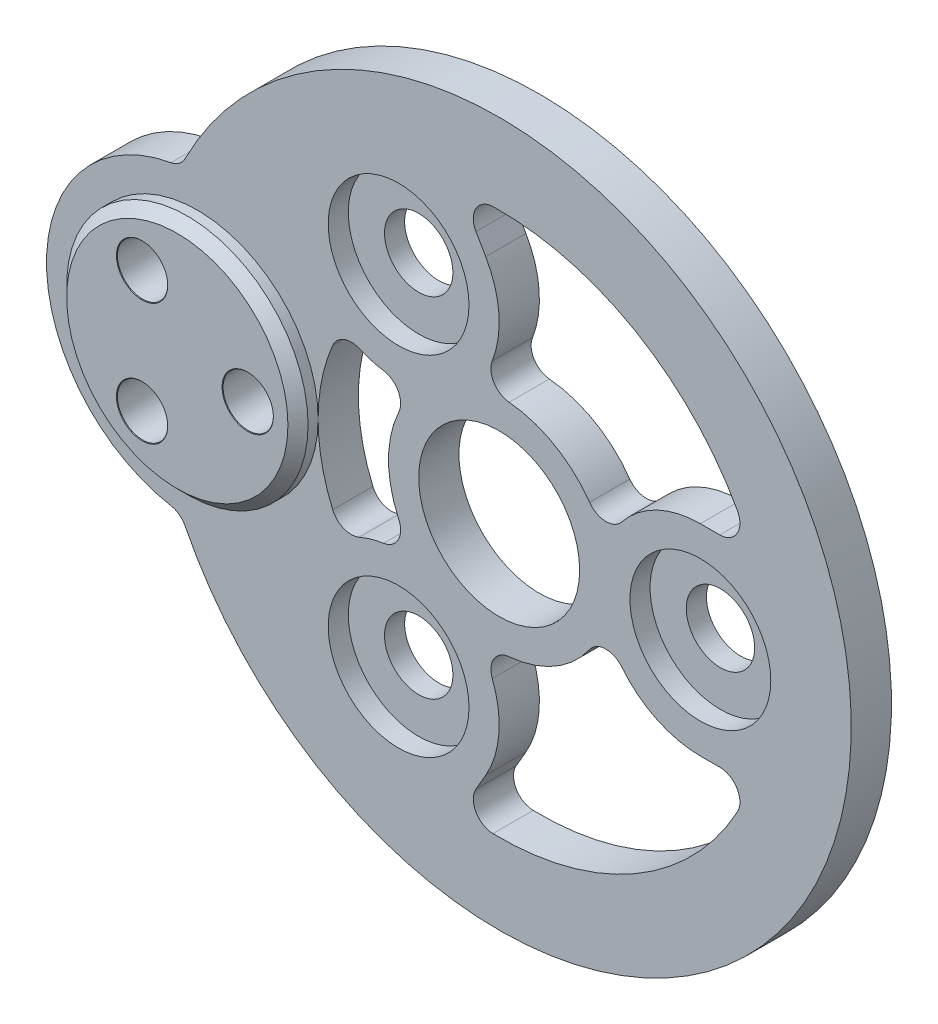
SolidWorks part; units mm, degrees
material "A2017"
ref_plane "正面" through (0, 0, 0) normal (0, 0, 1) x (1, 0, 0)
ref_plane "平面" through (0, 0, 0) normal (0, 1, 0) x (1, 0, 0)
ref_plane "右側面" through (0, 0, 0) normal (1, 0, 0) x (0, 0, -1)
sketch "ｽｹｯﾁ1" plane through (0, 0, 0) normal (0, 0, 1) x (1, 0, 0)
  line L0 (-15, 0) -> (0, 0) construction
  circle A0 centre (0, 0) radius 4
  arc A1 (-4.5, -6) -> (-4.5, 6) centre (0, 0) ccw
  arc A2 (-10.5, 6) -> (-10.5, -6) centre (-15, 0) ccw
  arc A3 (-10.5, 6) -> (-4.5, 6) centre (-7.5, 10) ccw
  arc A4 (-10.5, -6) -> (-4.5, -6) centre (-7.5, -10) cw
  dimension "D1" = 8
  dimension "D2" = 15
  dimension "D3" = 15
  dimension "D4" = 5
extrude "ﾎﾞｽ - 押し出し1" add sketch "ｽｹｯﾁ1" along normal blind 2
sketch "ｽｹｯﾁ6" plane through (0, 0, 2) normal (0, 0, 1) x (1, 0, 0)
  circle A0 centre (-15, 0) radius 6
  dimension "D1" = 12
extrude "ﾎﾞｽ - 押し出し3" add sketch "ｽｹｯﾁ6" along normal blind 1
sketch "ｽｹｯﾁ2" plane through (0, 0, 3) normal (0, 0, 1) x (1, 0, 0)
  circle A0 centre (-15, 0) radius 5 construction
  circle A1 centre (-11.5, 0) radius 1.5 construction
  circle A2 centre (-11.5, 0) radius 0.5
  dimension "D1" = 10
  dimension "D2" = 3
  dimension "D3" = 1
extrude "ｶｯﾄ - 押し出し1" cut sketch "ｽｹｯﾁ2" against normal blind 2
hole_wizard "M3x0.5 ねじ穴1" positions "ｽｹｯﾁ3" profile "ｽｹｯﾁ4" tap size "M3x0.5" standard "JIS" end condition through all
sketch "ｽｹｯﾁ3" plane through (0, 0, 3) normal (0, 0, 1) x (1, 0, 0)
  point P0 (-11.5, 0)
sketch "ｽｹｯﾁ4" plane through (-11.5, 0, 3) normal (1, 0, 0) x (0, -1, 0)
  line L0 (0, 0) -> (0, 3)
  line L1 (0, 3) -> (1.525, 3)
  line L2 (1.25, 2.725) -> (1.25, 0.025)
  line L3 (1.25, 0.025) -> (1.275, 0)
  line L5 (1.275, 0) -> (0, 0)
  line L6 (-1.25, 0.025) -> (-1.275, 0) construction
  line L7 (1.525, 3) -> (1.25, 2.725)
  line L8 (-1.525, 3) -> (-1.25, 2.725) construction
  line L11 (0, -6.35) -> (0, 107.95) construction
  dimension "次ｻｰﾌｪｽまでのねじ下穴ﾄﾞﾘﾙ直径" = 2.5
  dimension "次ｻｰﾌｪｽまでのねじ下穴ﾄﾞﾘﾙの深さ" = 3
  dimension "表面の皿穴の直径" = 2.55
  dimension "表面の皿穴の角度" = 90
  dimension "裏面の皿穴の直径" = 3.05
  dimension "裏面の皿穴の角度" = 90
cosmetic thread "穴のねじ山1" parameters "D2"=3
pattern_circular "円形ﾊﾟﾀｰﾝ1" count 3 over 360 about axis through (-15, 0, 2) along (0, 0, -1) of "M3x0.5 ねじ穴1"
chamfer "面取り1" distance 0.5 angle 45 1 edges at (-9, 0, 3)
chamfer "面取り2" [suppressed] distance 0.5 angle 45
chamfer "面取り3" [suppressed] distance 0.1 angle 45
sketch "ｽｹｯﾁ7" plane through (0, 0, 2) normal (0, 0, 1) x (1, 0, 0)
  circle A0 centre (0, 0) radius 17.5
  arc A5 (-10.5, 6) -> (-4.5, 6) centre (-7.5, 10) ccw
  arc A6 (-10.5, 6) -> (-10.5, -6) centre (-15, 0) ccw
  arc A7 (-4.5, -6) -> (-10.5, -6) centre (-7.5, -10) ccw
  arc A8 (-4.5, -6) -> (-4.5, 6) centre (0, 0) ccw
  arc A9 (-10.5, 6) -> (-4.5, 6) centre (-7.5, 10) ccw
  arc A10 (-10.5, 6) -> (-10.5, -6) centre (-15, 0) ccw
  arc A11 (-4.5, -6) -> (-10.5, -6) centre (-7.5, -10) ccw
  arc A12 (-4.5, -6) -> (-4.5, 6) centre (0, 0) ccw
  circle M5 centre (-15, 0) radius 6
  arc M6 (-4.5, 6) -> (-10.5, 6) centre (-7.5, 10) cw
  arc M7 (-10.5, 6) -> (-10.5, -6) centre (-15, 0) ccw
  arc M8 (-10.5, -6) -> (-4.5, -6) centre (-7.5, -10) cw
  arc M9 (-4.5, -6) -> (-4.5, 6) centre (0, 0) ccw
  circle M10 centre (0, 0) radius 4
  dimension "D1" = 35
  dimension "D2" = 0
extrude "ﾎﾞｽ - 押し出し4" add sketch "ｽｹｯﾁ7" against normal up to surface (2 mm away) contours A0 M7 M6 M9 M8 | A0 M7 M5 M8 M9 M6 M10 region at (3.7133, -16.6066, 2) region at (-13.1023, 6.9629, 2) up to face at (-17.5125, 4.3518, 0)
hole_wizard "M3 すきま穴1" positions "ｽｹｯﾁ9" profile "ｽｹｯﾁ10" hole size "M3" standard "JIS" end condition through all
sketch "ｽｹｯﾁ9" plane through (0, 0, 2) normal (0, 0, 1) x (1, 0, 0)
  point P0 (-5, 8.6603)
  point P3 (-5, -8.6603)
  point P6 (10, 0)
sketch "ｽｹｯﾁ10" plane through (-5, 8.6603, 2) normal (1, 0, 0) x (0, -1, 0)
  line L0 (0, 0) -> (0, 2)
  line L1 (0, 2) -> (1.7, 2)
  line L2 (1.7, 2) -> (1.7, 0)
  line L5 (1.7, 0) -> (0, 0)
  line L11 (0, -6.35) -> (0, 107.95) construction
  dimension "通し穴の直径" = 3.4
  dimension "通し穴の深さ" = 2
sketch "ｽｹｯﾁ11" plane through (0, 0, 2) normal (0, 0, 1) x (1, 0, 0)
  circle A0 centre (-5, 8.6603) radius 3.5
  circle A1 centre (10, 0) radius 3.5
  circle A2 centre (-5, -8.6603) radius 3.5
  point P11 (0, 0)
  dimension "D1" = 7
  dimension "D2" = 3
extrude "ｶｯﾄ - 押し出し3" cut sketch "ｽｹｯﾁ11" against normal blind 1
sketch "ｽｹｯﾁ12" plane through (0, 0, 2) normal (0, 0, 1) x (1, 0, 0)
  line L0 (10, 0) -> (13.5, 0) construction
  line L1 (10, 5) -> (13.5, 5)
  line L2 (10, -5) -> (13.5, -5)
  line L3 (-5, -8.6603) -> (-6.75, -11.6913) construction
  line L4 (-0.6699, -11.1603) -> (-2.4199, -14.1913)
  line L5 (-9.3301, -6.1603) -> (-11.0801, -9.1913)
  line L6 (-5, 8.6603) -> (-6.75, 11.6913) construction
  line L7 (-9.3301, 6.1603) -> (-11.0801, 9.1913)
  line L8 (-0.6699, 11.1603) -> (-2.4199, 14.1913)
  circle A0 centre (0, 0) radius 13.5
  circle A1 centre (0, 0) radius 5.5
  arc A2 (10, 5) -> (10, -5) centre (10, 0) ccw
  arc A3 (13.5, -5) -> (13.5, 5) centre (13.5, 0) ccw
  arc A4 (-0.6699, -11.1603) -> (-9.3301, -6.1603) centre (-5, -8.6603) ccw
  arc A5 (-11.0801, -9.1913) -> (-2.4199, -14.1913) centre (-6.75, -11.6913) ccw
  arc A6 (-9.3301, 6.1603) -> (-0.6699, 11.1603) centre (-5, 8.6603) ccw
  arc A7 (-2.4199, 14.1913) -> (-11.0801, 9.1913) centre (-6.75, 11.6913) ccw
  arc A8 (-0.3439, 6.8379) -> (0.4969, 5.4775) centre (0.5873, 6.4734) ccw
  arc A9 (4.4952, 3.1691) -> (6.0938, 3.1211) centre (5.3125, 3.7453) ccw
  arc A10 (0.4969, -5.4775) -> (-0.3439, -6.8379) centre (0.5873, -6.4734) ccw
  arc A11 (6.0938, -3.1211) -> (4.4952, -3.1691) centre (5.3125, -3.7453) ccw
  arc A12 (-4.9921, 2.3084) -> (-5.7498, 3.7168) centre (-5.8998, 2.7281) ccw
  arc A13 (-5.7498, -3.7168) -> (-4.9921, -2.3084) centre (-5.8998, -2.7281) ccw
  arc A14 (-7.7884, 4.51) -> (-7.7884, -4.51) centre (0, 0) ccw
  circle A15 centre (-15, 0) radius 6 construction
  point P7 (11.75, 0)
  point P16 (-5.875, -10.1758)
  point P23 (-5.875, 10.1758)
  point P28 (0, 0)
  point P48 (0, 0)
  dimension "D1" = 27
  dimension "D2" = 11
  dimension "D5" = 1
  dimension "D3" = 10
  dimension "D4" = 3
  dimension "D6" = 3
extrude "ｶｯﾄ - 押し出し4" cut sketch "ｽｹｯﾁ12" against normal through all contours A1 A9 A2 L1 A0 L8 A6 A8 | A2 A11 A1 A10 A4 L4 A0 L2 | A6 A14 A4 A13 A1 A12 region at (4.8059, 8.3241, 2) region at (4.8059, -8.3241, 2) region at (-7.0052, 0, 2)
fillet "ﾌｨﾚｯﾄ1" radius 1 6 edges at (12.5399, -5, 1) (-1.9398, -13.3599, 1) (12.5399, 5, 1) (-7.7884, -4.51, 1) (-7.7884, 4.51, 1) (-1.9398, 13.3599, 1)
fillet "ﾌｨﾚｯﾄ2" radius 1 2 edges at (-15.8333, -7.4536, 1) (-15.8333, 7.4536, 1)
